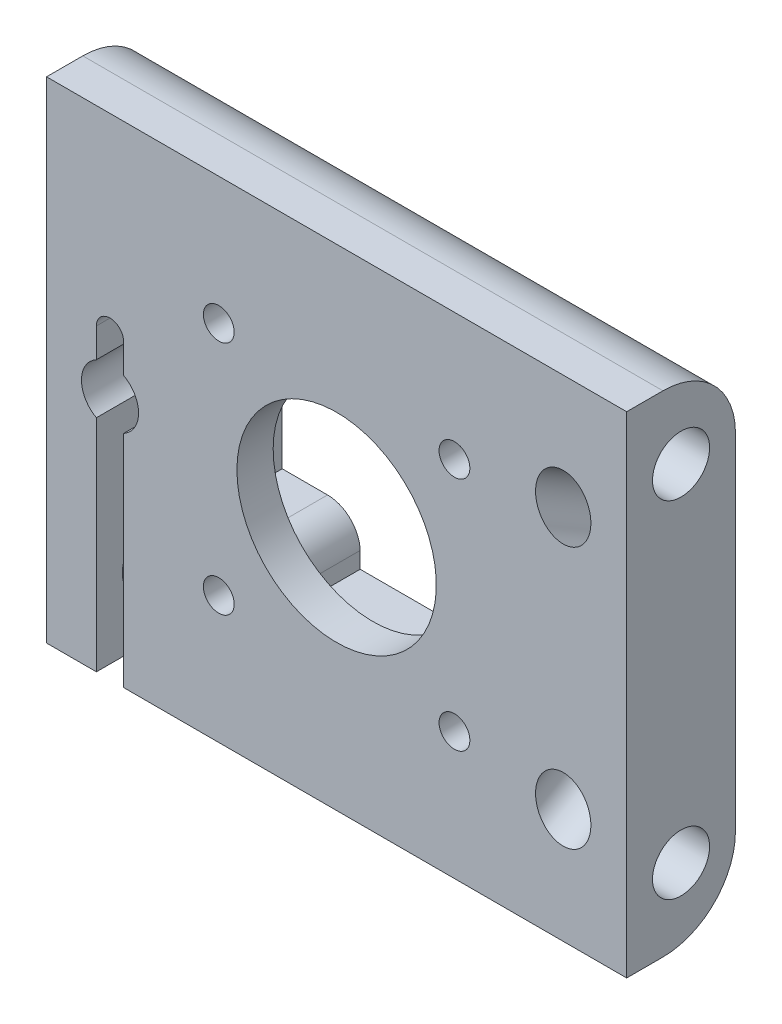
SolidWorks part; units mm, degrees
ref_plane "Front Plane" through (0, 0, 0) normal (0, 0, 1) x (1, 0, 0)
ref_plane "Top Plane" through (0, 0, 0) normal (0, 1, 0) x (1, 0, 0)
ref_plane "Right Plane" through (0, 0, 0) normal (1, 0, 0) x (0, 0, -1)
sketch "Sketch1" plane through (0, 0, 0) normal (0, 0, 1) x (1, 0, 0)
  line L1 (0, 0) -> (64, 0)
  line L2 (0, 0) -> (0, 54.105)
  line L3 (0, 54.105) -> (64, 54.105)
  line L4 (64, 0) -> (64, 54.105)
  dimension "D1" = 54.105
  dimension "D2" = 64
extrude "Boss-Extrude1" add sketch "Sketch1" along normal blind 12
sketch "Sketch2" plane through (0, 0, 0) normal (1, 0, 0) x (0, 0, -1)
  line L0 (-12, 27.0525) -> (0, 27.0525) construction
  line L1 (-12, 0) -> (-12, 54.105) construction
  line L2 (0, 0) -> (0, 54.105) construction
  circle A0 centre (-6, 46.105) radius 3.15
  circle A1 centre (-6, 8) radius 3.15
  dimension "D2" = 6.3
  dimension "D1" = 6
  dimension "D3" = 19.0525
extrude "Cut-Extrude1" cut sketch "Sketch2" along normal through all
fillet "Fillet1" radius 8 2 edges at (32, 0, 0) (32, 54.105, 0)
sketch "Sketch3" plane through (0, 0, 0) normal (0, 0, -1) x (-1, 0, 0)
  line L0 (-64, 27.0525) -> (0, 27.0525) construction
  line L1 (-64, 8) -> (-64, 46.105) construction
  line L2 (0, 46.105) -> (0, 8) construction
  line L3 (-8.5, 0) -> (-8.5, 24.2826)
  line L5 (-5.5, 33.0525) -> (-5.5, 29.8224)
  line L6 (0, 0) -> (-64, 0) construction
  line L7 (-8.5, 0) -> (-5.5, 0)
  line L8 (-8.5, 29.8224) -> (-8.5, 33.0525)
  line L9 (-5.5, 24.2826) -> (-5.5, 0)
  arc A0 (-8.5, 29.8224) -> (-8.5, 24.2826) centre (-7, 27.0525) ccw
  circle A1 centre (-32, 27.0525) radius 11
  circle A2 centre (-19, 40.0525) radius 1.7
  circle A3 centre (-19, 14.0525) radius 1.7
  arc A4 (-5.5, 24.2826) -> (-5.5, 29.8224) centre (-7, 27.0525) ccw
  arc A5 (-5.5, 33.0525) -> (-8.5, 33.0525) centre (-7, 33.0525) ccw
  circle A6 centre (-45, 14.0525) radius 1.7
  circle A7 centre (-45, 40.0525) radius 1.7
  dimension "D1" = 22
  dimension "D2" = 6.3
  dimension "D5" = 3.4
  dimension "D6" = 1.5
  dimension "D7" = 13
  dimension "D10" = 13
  dimension "D3" = 7
  dimension "D4" = 25
  dimension "D8" = 3
  dimension "D9" = 6
  dimension "D11" = 4
extrude "Cut-Extrude2" cut sketch "Sketch3" against normal through all
sketch "Sketch5" plane through (0, 0, 0) normal (0, 0, -1) x (-1, 0, 0)
  line L0 (-64, 27.0525) -> (-29.1332, 27.0525) construction
  line L1 (-19, 17.6525) -> (-14, 17.6525)
  line L2 (-50, 36.4525) -> (-50, 17.6525)
  line L4 (-14, 36.4525) -> (-14, 17.6525)
  line L5 (-64, 8) -> (-64, 46.105) construction
  line L7 (0, 46.105) -> (0, 8) construction
  line L8 (-41.4013, 41.7525) -> (-22.5987, 41.7525)
  line L9 (-22.5987, 41.7525) -> (-22.5987, 39.955)
  line L10 (-41.4013, 39.955) -> (-41.4013, 41.7525)
  line L11 (-45, 36.4525) -> (-50, 36.4525)
  line L12 (-19, 36.4525) -> (-14, 36.4525)
  line L13 (-45, 17.6525) -> (-50, 17.6525)
  line L14 (-41.4013, 14.15) -> (-41.4013, 12.3525)
  line L15 (-22.5987, 12.3525) -> (-22.5987, 14.15)
  line L16 (-41.4013, 12.3525) -> (-22.5987, 12.3525)
  arc A0 (-45, 36.4525) -> (-41.4013, 39.955) centre (-45, 40.0525) ccw
  arc A1 (-22.5987, 39.955) -> (-19, 36.4525) centre (-19, 40.0525) ccw
  circle A2 centre (-45, 40.0525) radius 1.7 construction
  circle A3 centre (-19, 40.0525) radius 1.7 construction
  arc A4 (-22.5987, 14.15) -> (-19, 17.6525) centre (-19, 14.0525) cw
  arc A5 (-45, 17.6525) -> (-41.4013, 14.15) centre (-45, 14.0525) cw
  dimension "D1" = 14
  dimension "D5" = 3.6
  dimension "D4" = 14
extrude "Cut-Extrude4" cut sketch "Sketch5" against normal offset from surface (8 mm away) 4 up to face at (43.3, 40.0525, 12)
sketch "Sketch4" plane through (0, 0, 0) normal (0, 0, -1) x (-1, 0, 0)
  circle A0 centre (-32, 27.0525) radius 6.7
  circle A1 centre (-32, 27.0525) radius 11 construction
  dimension "D1" = 13.4
extrude "Cut-Extrude3" [suppressed] cut sketch "Sketch4" against normal offset from surface (9 mm away) 3
ref_axis "Axis1" through (64, 8, 6) along (-1, 0, 0)
ref_plane "Plane1" through (0, -0.5981, 1.0359) normal (0, 0.5, -0.866) x (1, 0, 0)
ref_axis "Axis2" through (32, 27.0525, 12) along (0, 0, -1)
ref_plane "Plane2" through (0, 27.0525, 0) normal (0, 1, 0) x (-1, 0, 0)
sketch "Sketch6" plane through (0, -0.5981, 1.0359) normal (0, 0.5, -0.866) x (1, 0, 0)
  line L0 (64, -9.9282) -> (8.5, -9.9282) construction
  line L1 (64, -6.9282) -> (64, -39.9281) construction
  circle A0 centre (57, -16.9282) radius 3.05
  dimension "D3" = 6.1
  dimension "D1" = 7
  dimension "D2" = 7
extrude "Cut-Extrude5" cut sketch "Sketch6" against normal through all and the other way blind 8
mirror "Mirror1" about plane through (0, 27.0525, 0) normal (0, 1, 0) of "Cut-Extrude5"
